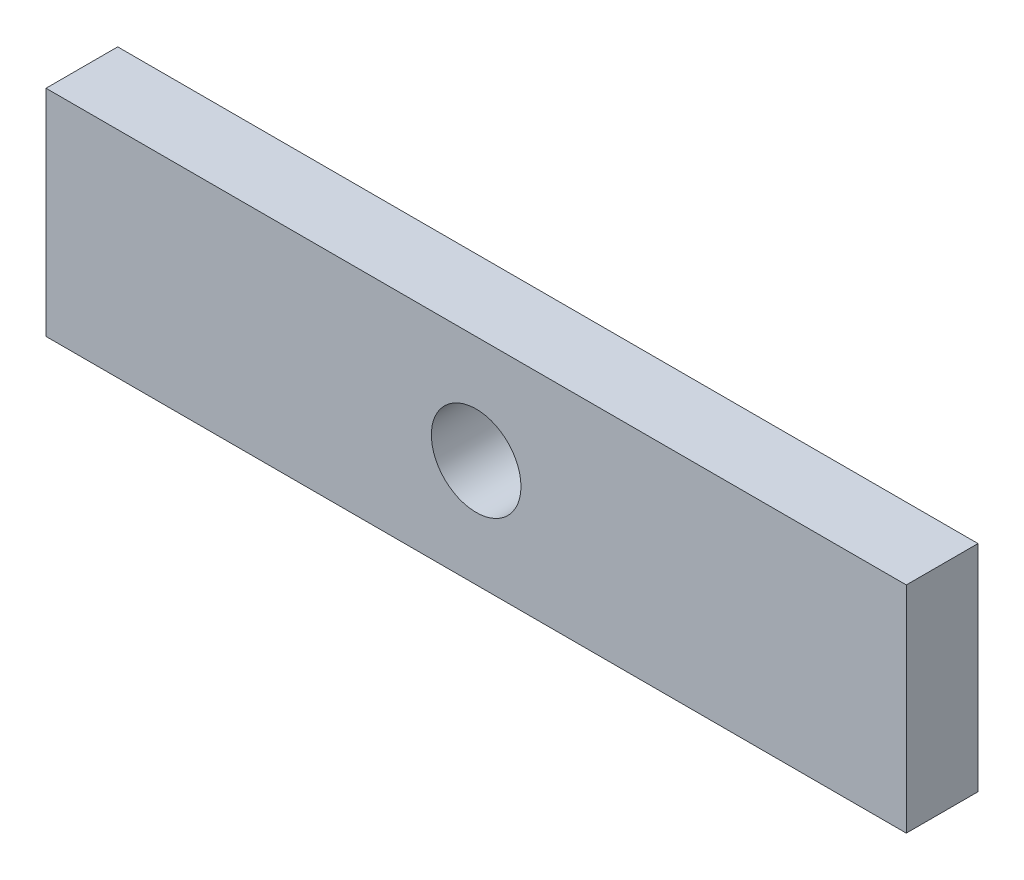
SolidWorks part; units mm, degrees
ref_plane "Front Plane" through (0, 0, 0) normal (0, 0, 1) x (1, 0, 0)
ref_plane "Top Plane" through (0, 0, 0) normal (0, 1, 0) x (1, 0, 0)
ref_plane "Right Plane" through (0, 0, 0) normal (1, 0, 0) x (0, 0, -1)
ref_plane "Plane1" through (0, 0, -20.3301) normal (0, 0, 1) x (1, 0, 0)
sketch "Sketch2" plane through (0, 0, -20.3301) normal (0, 0, 1) x (1, 0, 0)
  line L0 (35.5918, -6.5527) -> (35.5918, -18.5467) construction
  line L1 (59.5918, -6.5527) -> (11.5918, -6.5527) construction
  line L2 (59.5918, -18.5467) -> (11.5918, -18.5467) construction
  line L4 (11.5918, -6.5527) -> (59.5918, -6.5527)
  line L5 (11.5918, -6.5527) -> (11.5918, -18.5467)
  line L6 (11.5918, -18.5467) -> (59.5918, -18.5467)
  line L7 (59.5918, -6.5527) -> (59.5918, -18.5467)
  circle A0 centre (35.5918, -12.5497) radius 2.5
  arc A2 (38.0917, -18.0008) -> (33.0919, -18.0008) centre (35.5918, -12.5497) ccw construction
  circle A3 centre (35.5918, -12.5497) radius 5.997 construction
  point P6 (35.5918, -6.5527)
  point P18 (35.5918, -18.5467)
  dimension "D1" = 48
extrude "Boss-Extrude1" add sketch "Sketch2" along normal blind 4
sketch "Sketch3" plane through (0, 0, -16.3301) normal (0, 0, 1) x (1, 0, 0)
  line L0 (11.5918, -18.5467) -> (59.5918, -18.5467) construction
  line L1 (59.5918, -6.5527) -> (24.7285, -6.5527)
  line L2 (59.5918, -6.5527) -> (59.5918, -18.5467)
  line L3 (59.5918, -18.5467) -> (24.7285, -18.5467)
  line L4 (24.7285, -6.5527) -> (24.7285, -18.5467)
  line L5 (35.5918, -6.5527) -> (35.5918, -18.5467) construction
  line L6 (59.5918, -6.5527) -> (11.5918, -6.5527) construction
  line L7 (11.5918, -18.5467) -> (46.455, -18.5467)
  line L8 (46.455, -6.5527) -> (46.455, -18.5467)
  line L9 (11.5918, -6.5527) -> (46.455, -6.5527)
  line L10 (11.5918, -6.5527) -> (11.5918, -18.5467)
extrude "Boss-Extrude2" add sketch "Sketch3" along normal blind 10 rebuild error yes
sketch "Sketch4" plane through (24.7285, 0, 0) normal (1, 0, 0) x (0, 0, -1)
  line L0 (-16.3301, -17.8674) -> (-6.3301, -29.8614) construction
  line L1 (-6.3301, -29.8614) -> (-6.3301, -17.8674) construction
  line L2 (-6.3301, -17.8674) -> (-16.3301, -29.8614) construction
  circle A0 centre (-11.3301, -23.8644) radius 1.5
  dimension "D1" = 3
extrude "Cut-Extrude1" cut sketch "Sketch4" against normal through all both and the other way through all rebuild error yes
